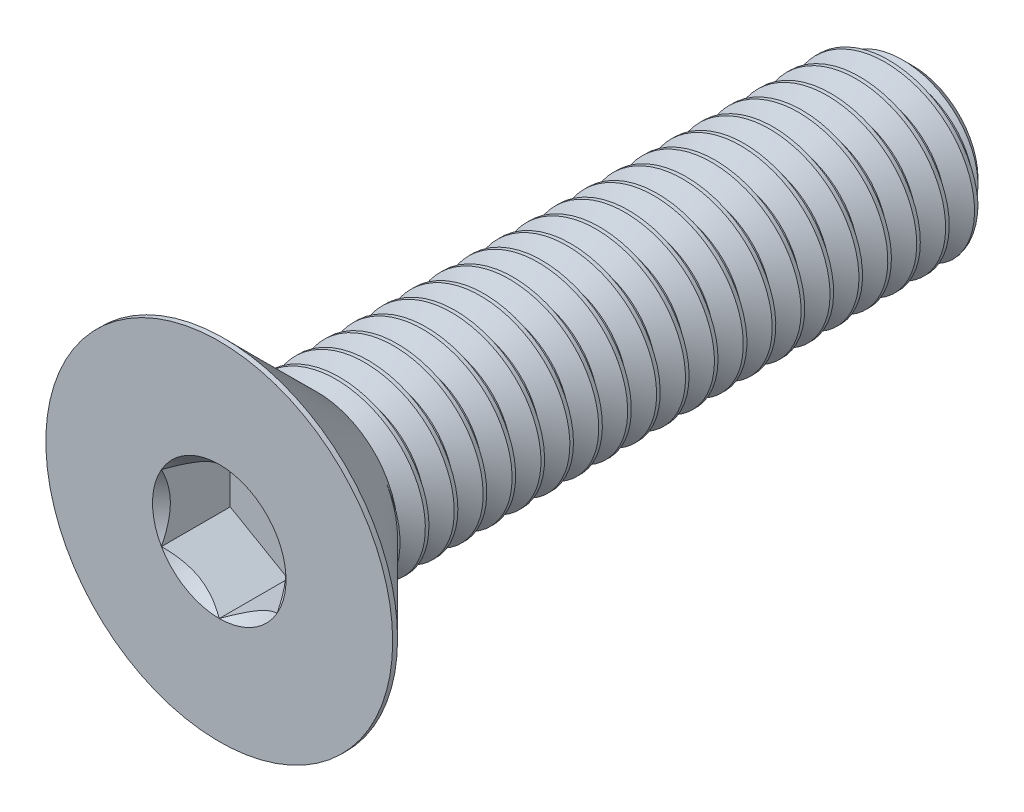
SolidWorks part; units mm, degrees
ref_plane "Front" through (0, 0, 0) normal (0, 0, 1) x (1, 0, 0)
ref_plane "Top" through (0, 0, 0) normal (0, 1, 0) x (1, 0, 0)
ref_plane "Right" through (0, 0, 0) normal (1, 0, 0) x (0, 0, -1)
sketch "Sketch11" plane through (0, 0, 0) normal (1, 0, 0) x (0, 0, -1)
  line L0 (-6, 3) -> (6, 3) construction
  line L5 (-6, 3) -> (-6, -3) construction
  line L6 (6, 1.5) -> (6, -1.5) construction
  line L7 (-5.99, 1) -> (-5.99, -1) construction
  line L8 (5.9688, 1.5541) -> (6.4688, 1.5541) construction
  line L9 (6.4688, 1.5541) -> (6.2188, 1.1211) construction
  line L10 (6.2188, 1.1211) -> (5.9688, 1.5541) construction
  line L11 (6.1875, 1.1752) -> (6.25, 1.1752) construction
  line L12 (6.2188, 1.1752) -> (6.2188, 1.1211) construction
  line L13 (5.9844, 1.5271) -> (6.4531, 1.5271) construction
  line L14 (6.2188, 1.5541) -> (6.2188, 1.5) construction
  line L15 (6, 1.5) -> (6.4375, 1.5) construction
  line L17 (-5.915, 3) -> (-2.915, 0) construction
  line L18 (-2.915, 0) -> (-5.915, -3) construction
  point P3 (-4.3, 3)
  point P8 (0, 3)
  point P21 (6.2188, 1.5271)
  point P26 (-6, 0)
  point P28 (-5.99, 0)
  point P29 (6, 0)
  dimension "Length" = 12
  dimension "Head Diameter" = 6
  dimension "Thread Major Diameter" = 3
  dimension "Head Height" = 1.7
  dimension "Drive Size" = 2
  dimension "Thread Pitch" = 0.5
  dimension "D1" = 0.0625
  dimension "D2" = 0.01
  dimension "D3" = 0.085
  dimension "Countersink Angle" = 90
sketch "Sketch1" plane through (0, 0, 0) normal (1, 0, 0) x (0, 0, -1)
  line L2 (-4.3, 1.5) -> (6, 1.5)
  line L3 (6, 1.5) -> (6, 0)
  line L4 (-4.81, 1.5) -> (-4.81, 0)
  line L5 (-4.3, 1.5) -> (-4.81, 1.5)
  line L6 (-6, 3) -> (-6, -3) construction
  line L7 (6, 1.5) -> (6, -1.5) construction
  line L8 (-4.81, 0) -> (6, 0)
  dimension "D1" = 1.19
revolve "Revolve1" add sketch "Sketch1" angle 360 mid plane about L8
chamfer "Chamfer1" distance 0.375 angle 45 1 edges at (1.5, 0, -6)
sketch "Sketch7" plane through (0, 0, 0) normal (1, 0, 0) x (0, 0, -1)
  line L2 (-6, 3) -> (-5.915, 3)
  line L5 (-4.3, 1.385) -> (-4.3, 0)
  line L6 (-6, 3) -> (-6, 0)
  line L8 (-6, 3) -> (-6, -3) construction
  line L9 (-6, 0) -> (-4.3, 0)
  line L12 (-5.915, 3) -> (-4.3, 1.385)
  line L13 (-5.915, 3) -> (-2.915, 0) construction
revolve "Revolve2" add sketch "Sketch7" angle 360 mid plane about L9 region at (0, 1.1696, 5.2571)
ref_plane "Plane1" through (0, 0, 4.3) normal (0, 0, 1) x (1, 0, 0)
sketch "Sketch5" plane through (0, 0, 6) normal (0, 0, 1) x (1, 0, 0)
  line L1 (1, -0.5774) -> (1, 0.5774)
  line L2 (1, 0.5774) -> (0, 1.1547)
  line L3 (0, 1.1547) -> (-1, 0.5774)
  line L4 (-1, 0.5774) -> (-1, -0.5774)
  line L5 (-1, -0.5774) -> (0, -1.1547)
  line L6 (0, -1.1547) -> (1, -0.5774)
  circle A0 centre (0, 0) radius 1 construction
extrude "Cut-Extrude2" cut sketch "Sketch5" against normal blind 1.19
sketch "Sketch6" plane through (0, 0, 6) normal (0, 0, -1) x (-1, 0, 0)
  circle A0 centre (0, 0) radius 1.1547
extrude "Cut-Extrude3" cut sketch "Sketch6" along normal blind 1.19 draft 45
sketch "Sketch12" plane through (0, 0, -6) normal (0, 0, -1) x (-1, 0, 0)
  circle A0 centre (0, 0) radius 1.5 construction
  circle A1 centre (0, 0) radius 1.5
curve "Helix/Spiral1" pitch 0.5 height 12 radius 1.5 centre (0, 0, -6) axis (0, 0, 1) start towards (0, 1, 0)
sketch "Sketch13" plane through (0, 0, 0) normal (1, 0, 0) x (0, 0, -1)
  line L0 (5.9844, 1.5271) -> (6.4531, 1.5271)
  line L1 (6.4531, 1.5271) -> (6.25, 1.1752)
  line L2 (6.25, 1.1752) -> (6.1875, 1.1752)
  line L3 (6.1875, 1.1752) -> (5.9844, 1.5271)
sweep "Cut-Sweep1" cut profiles "Sketch13" path "Helix/Spiral1" align with end faces yes
combine bodies "Combine1" operation type add bodies to combine 113 127
equation "\"D1@Chamfer1\"=\"Thread Pitch@Sketch11\" * .75"
equation "\"D1@Cut-Extrude2\"= \"Head Height@Sketch11\" * .7"
equation "\"D1@Cut-Extrude3\" = \"D1@Cut-Extrude2\""
equation "\"D1@Sketch11\"=\"Thread Pitch@Sketch11\"/8"
equation "\"D3@Sketch11\"=\"Head Height@Sketch11\"*.05"
equation "\"D4@Helix/Spiral1\"=\"Thread Pitch@Sketch11\""
equation "\"D1@Sketch1\"=\"Head Height@Sketch11\"*.7"
equation "\"D3@Helix/Spiral1\"=\"Length@Sketch11\""
